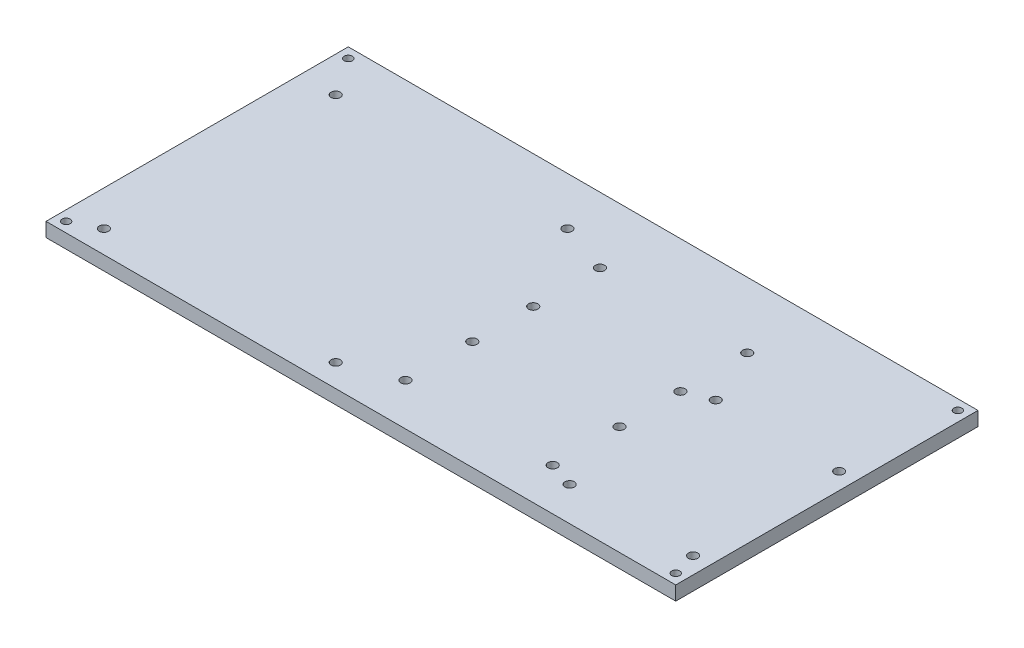
SolidWorks part; units mm, degrees
ref_plane "Front Plane" through (0, 0, 0) normal (0, 0, 1) x (1, 0, 0)
ref_plane "Top Plane" through (0, 0, 0) normal (0, 1, 0) x (1, 0, 0)
ref_plane "Right Plane" through (0, 0, 0) normal (1, 0, 0) x (0, 0, -1)
sketch "Sketch1" plane through (0, 0, 0) normal (0, 1, 0) x (1, 0, 0)
  line L1 (-125, -60) -> (125, -60)
  line L2 (-125, -60) -> (-125, 60)
  line L3 (-125, 60) -> (125, 60)
  line L4 (125, -60) -> (125, 60)
  line L5 (-125, -60) -> (125, 60) construction
  line L6 (-125, 60) -> (125, -60) construction
  point P0 (0, 0)
  dimension "D1" = 120
  dimension "D2" = 250
extrude "Boss-Extrude1" add sketch "Sketch1" along normal blind 5.588
hole_wizard "Ø3.0mm Clearance Dowel Hole2" positions "Sketch4" profile "Sketch5" hole size "Ø3.0" standard "ANSI Metric" end condition through all
sketch "Sketch4" plane through (-44.961, 0, -163.6882) normal (0, -1, 0) x (-1, 0, 0)
  point P0 (-45.936, -156.2482)
  point P3 (-25.961, -122.6882)
  point P6 (-45.936, -129.7282)
  point P9 (-45.936, -180.4282)
  point P12 (-45.936, -206.9482)
  point P15 (-25.961, -214.6882)
  point P18 (66.039, -214.6882)
  point P51 (-104.386, -206.9482)
  point P54 (-104.386, -180.4282)
  point P57 (-104.386, -156.2482)
  point P60 (-104.386, -129.7282)
  point P63 (-163.3388, -210.1882)
  point P66 (-163.3388, -152.1882)
  point P69 (-114.3388, -152.1882)
  point P72 (-114.3388, -210.1882)
  point P81 (66.039, -122.6882)
sketch "Sketch5" plane through (0.975, 0, -7.44) normal (1, 0, 0) x (0, 0, -1)
  line L0 (0, 0) -> (0, 5.588)
  line L1 (0, 5.588) -> (1.85, 5.588)
  line L2 (1.85, 5.588) -> (1.85, 0)
  line L3 (1.85, 0) -> (0, 0)
  line L4 (0, -6.35) -> (0, 107.95) construction
  dimension "Thru Hole Dia." = 3.7
  dimension "Thru Hole Depth" = 5.588
sketch "Sketch6" plane through (0, 5.588, 0) normal (0, 1, 0) x (1, 0, 0)
  line L8 (121, -56) -> (121, 56)
  line L9 (-121, -56) -> (121, -56)
  line L10 (-121, 56) -> (-121, -56)
  line L11 (121, 56) -> (-121, 56)
  line L12 (121, -56) -> (121, 56) construction
  line L13 (-121, -56) -> (121, -56) construction
  line L14 (-121, 56) -> (-121, -56) construction
  line L15 (121, 56) -> (-121, 56) construction
  circle A0 centre (-121, 56) radius 1.6
  circle A1 centre (-121, -56) radius 1.6
  circle A2 centre (121, -56) radius 1.6
  circle A3 centre (121, 56) radius 1.6
  dimension "D2" = 3.2
  dimension "D1" = 4
extrude "Cut-Extrude1" cut sketch "Sketch6" against normal through all
